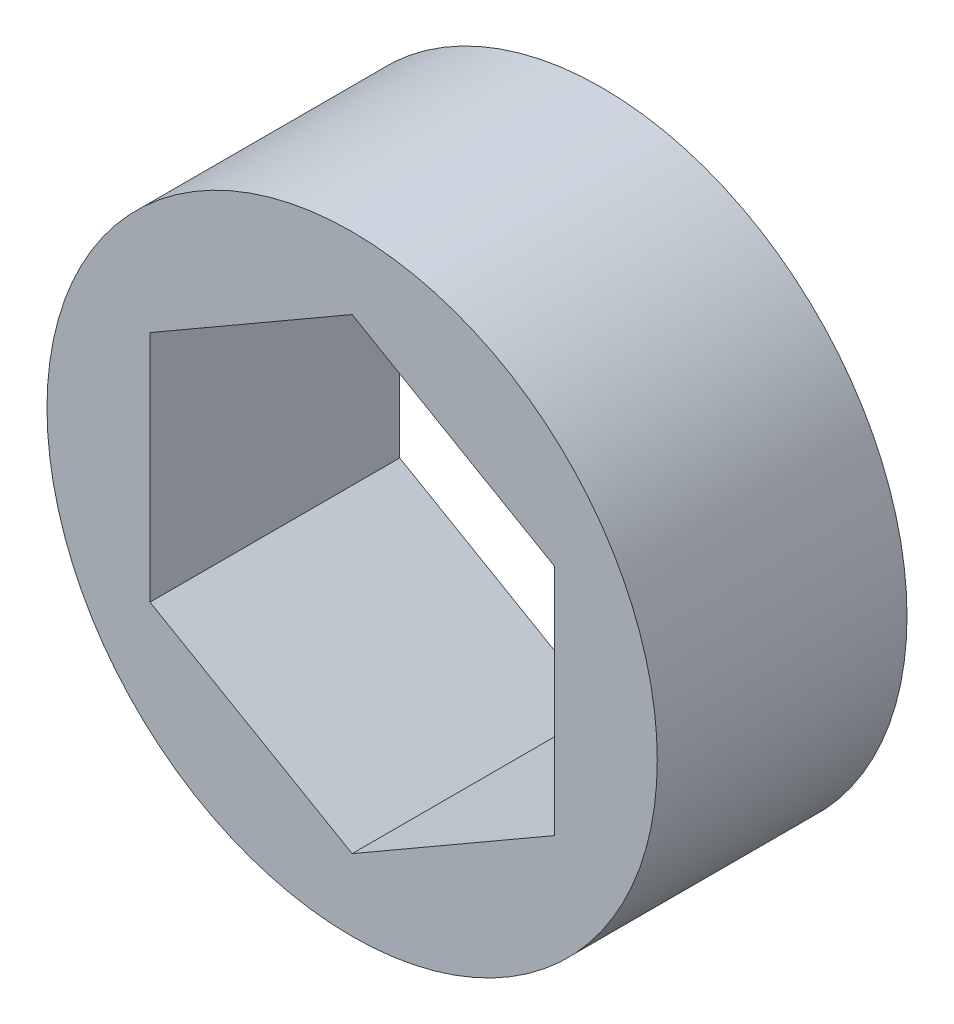
SolidWorks part; units mm, degrees
material "Nylon 101"
ref_plane "Front Plane" through (0, 0, 0) normal (0, 0, 1) x (1, 0, 0)
ref_plane "Top Plane" through (0, 0, 0) normal (0, 1, 0) x (1, 0, 0)
ref_plane "Right Plane" through (0, 0, 0) normal (1, 0, 0) x (0, 0, -1)
sketch "Sketch1" plane through (0, 0, 0) normal (0, 0, 1) x (1, 0, 0)
  line L1 (6.731, 3.8861) -> (0, 7.7723)
  line L2 (0, 7.7723) -> (-6.731, 3.8861)
  line L3 (-6.731, 3.8861) -> (-6.731, -3.8861)
  line L4 (-6.731, -3.8861) -> (0, -7.7723)
  line L5 (0, -7.7723) -> (6.731, -3.8861)
  line L6 (6.731, -3.8861) -> (6.731, 3.8861)
  circle A0 centre (0, 0) radius 6.731 construction
  circle A1 centre (0, 0) radius 10.16
  dimension "D1" = 13.462
  dimension "D2" = 20.32
extrude "Boss-Extrude1" add sketch "Sketch1" along normal blind 8.3145
